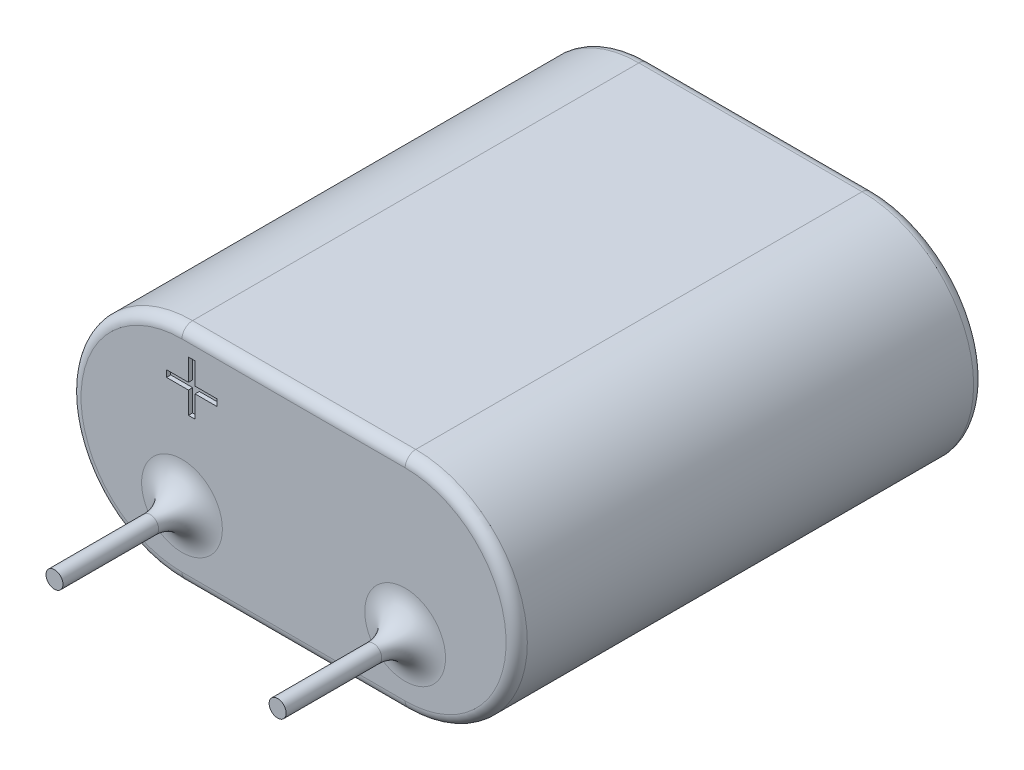
SolidWorks part; units mm, degrees
ref_plane "Front Plane" through (0, 0, 0) normal (0, 0, 1) x (1, 0, 0)
ref_plane "Top Plane" through (0, 0, 0) normal (0, 1, 0) x (1, 0, 0)
ref_plane "Right Plane" through (0, 0, 0) normal (1, 0, 0) x (0, 0, -1)
sketch "Sketch1" plane through (0, 0, 0) normal (0, 0, 1) x (1, 0, 0)
  line L0 (0, 5.25) -> (10.5, 5.25)
  line L1 (0, -5.25) -> (10.5, -5.25)
  arc A0 (0, 5.25) -> (0, -5.25) centre (0, 0) ccw
  arc A1 (10.5, -5.25) -> (10.5, 5.25) centre (10.5, 0) ccw
  dimension "D1" = 10.5
  dimension "D2" = 10.5
extrude "Boss-Extrude1" add sketch "Sketch1" against normal blind 22
sketch "Sketch2" plane through (0, 0, 0) normal (0, 0, 1) x (1, 0, 0)
  line L0 (0, 0) -> (0, 50000) construction
  line L1 (10.5, 0) -> (10.5, 50000) construction
  line L2 (0, -5.25) -> (10.5, -5.25) construction
  arc A0 (10.5, -5.25) -> (10.5, 5.25) centre (10.5, 0) ccw construction
  arc A1 (10.5, -5.25) -> (10.5, 5.25) centre (10.5, 0) ccw construction
  circle A2 centre (0, -2.05) radius 0.4
  circle A3 centre (10.5, -2.05) radius 0.4
  dimension "D1" = 0.8
  dimension "D2" = 3.2
  dimension "D3" = 10.5
ref_point "Point1"
ref_point "Point2"
ref_axis "Axis1" through (0, 0, 0) along (0, 1, 0)
ref_plane "Plane1" through (0, 0, 0) normal (1, 0, 0) x (0, 1, 0)
sketch "Sketch3" plane through (0, 0, 0) normal (1, 0, 0) x (0, 1, 0)
  line L0 (-2.05, 0) -> (-2.05, 6)
  point P2 (0, 0)
sweep "Sweep1" add profiles "Sketch2" path "Sketch3"
fillet "Fillet1" radius 1.5 2 edges at (10.9, -2.05, 0) (0.4, -2.05, 0)
fillet "Fillet2" radius 0.5 8 edges at (5.25, -5.25, -22) (15.75, 0, -22) (5.25, 5.25, -22) (-5.25, 0, -22) (5.25, 5.25, 0) (15.75, 0, 0) (5.25, -5.25, 0) (-5.25, 0, 0)
sketch "Sketch4" plane through (0, 0, 0) normal (0, 0, 1) x (1, 0, 0)
  line L1 (-1, 1.25) -> (3, 1.25) construction
  line L2 (0, 5.25) -> (10.5, 5.25) construction
  line L5 (0, -11) -> (0, 11) construction
  text T0 "+\r\n"
  dimension "D1" = 4
  dimension "D2" = 4
  dimension "D3" = 1
extrude "Cut-Extrude1" cut sketch "Sketch4" against normal blind 0.2
